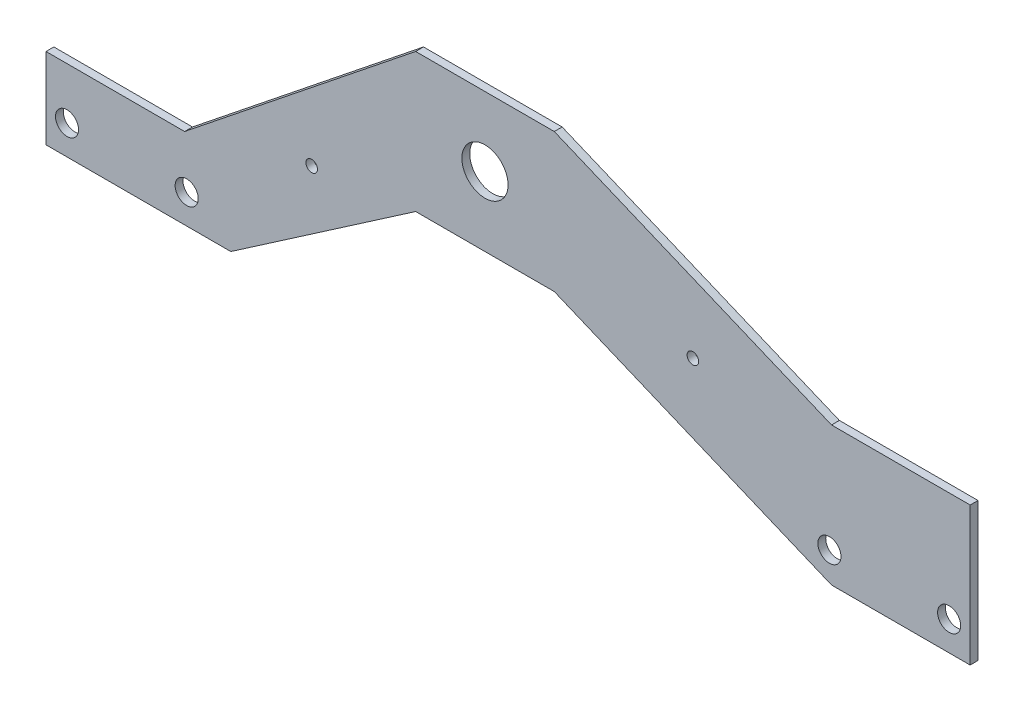
SolidWorks part; units mm, degrees
note: The reader was unsure of these and kept them because the rebuilt part matched: thickness of "Base-Flange1", "Sheet-Metal1", "Sheet-Metal2", "Sheet-Metal4".
material "1060 Alloy"
ref_plane "Front Plane" through (0, 0, 0) normal (0, 0, 1) x (1, 0, 0)
ref_plane "Top Plane" through (0, 0, 0) normal (0, 1, 0) x (1, 0, 0)
ref_plane "Right Plane" through (0, 0, 0) normal (1, 0, 0) x (0, 0, -1)
sketch "Sketch1" plane through (0, 0, 0) normal (0, 0, 1) x (1, 0, 0)
  line L0 (0, 0) -> (0, -35000)
  line L1 (0, -35000) -> (80000, -35000)
  line L2 (80000, -35000) -> (160000, 20000)
  line L3 (160000, 20000) -> (220000, 20000)
  line L4 (220000, 20000) -> (340000, -30000)
  line L5 (340000, -30000) -> (400000, -30000)
  line L6 (400000, -30000) -> (400000, 30000)
  line L7 (400000, 30000) -> (340000, 30000)
  line L8 (340000, 30000) -> (220000, 80000)
  line L9 (220000, 80000) -> (160000, 80000)
  line L10 (0, 0) -> (60000, 0)
  line L11 (160000, 80000) -> (60000, 0)
  line L12 (190000, 80000) -> (190000, 20000) construction
  line L13 (220000, 80000) -> (220000, 20000) construction
  line L14 (340000, 30000) -> (340000, -30000) construction
  line L15 (220000, 50000) -> (340000, 0) construction
  line L16 (100643.9259, 32515.1407) -> (129356.0741, -3375.0446) construction
  line L17 (115000, 14570.048) -> (190000, 50000) construction
  circle A0 centre (190000, 50000) radius 10000
  circle A1 centre (280000, 25000) radius 2500
  circle A2 centre (115000, 14570.048) radius 2500
  dimension "D12" = 20000
  dimension "D13" = 5000
  dimension "D14" = 5000
  dimension "D1" = 35000
  dimension "D2" = 80000
  dimension "D3" = 115000
  dimension "D4" = 60000
  dimension "D5" = 110000
  dimension "D6" = 60000
  dimension "D7" = 60000
  dimension "D8" = 60000
  dimension "D9" = 120000
  dimension "D10" = 80000
  dimension "D11" = 75000
base flange "Base-Flange1" sketch "Sketch1" thickness 3400 reverse thickness direction no parameters "D1"=0.7366
scale "Scale1" scale about centroid uniform scaling yes scale factor 0.001
sketch "Sketch2" plane through (0, 0, -1701.7) normal (0, 0, -1) x (-1, 0, 0)
  line L0 (-215477.869, 18112.8987) -> (-215477.869, 18077.8987)
  line L1 (-215477.869, 18077.8987) -> (-215557.869, 18077.8987)
  line L2 (-215512.869, 17958.5355) -> (-215512.869, 18112.8987) construction
  line L3 (-215512.869, 18090.5987) -> (-215538.769, 18090.5987) construction
  line L4 (-215537.869, 18112.8987) -> (-215477.869, 18112.8987) construction
  line L5 (-215477.869, 18112.8987) -> (-215557.869, 18112.8987)
  line L6 (-215877.869, 18082.8987) -> (-215842.869, 18082.8987)
  line L7 (-215842.869, 18082.8987) -> (-215842.869, 18095.5987) construction
  line L8 (-215842.869, 18095.5987) -> (-215868.769, 18095.5987) construction
  line L9 (-215557.869, 18112.8987) -> (-215557.869, 18077.8987)
  circle A0 centre (-215538.769, 18090.5987) radius 5
  circle A1 centre (-215486.969, 18090.5987) radius 5
  circle A2 centre (-215868.769, 18095.5987) radius 5
  circle A3 centre (-215816.969, 18095.5987) radius 5
  dimension "D1" = 25.9
  dimension "D2" = 25.9
  dimension "D3" = 12.7
  dimension "D4" = 35
  dimension "D5" = 12.7
  dimension "D6" = 35
extrude "Cut-Extrude1" cut sketch "Sketch2" against normal through all contours A1 | A0 | A3 | A2 normal cut yes
sketch "Bend-Lines1" [suppressed] plane through (0, 0, 0) normal (0, 1, 0) x (1, 0, 0)
sketch "Bounding-Box1" [suppressed] plane through (0, 0, 0) normal (0, 1, 0) x (1, 0, 0)
sheet metal parameters "Sheet-Metal1" thickness 3400 parameters "D1"=0.7366
flat pattern "Flat-Pattern1" [suppressed]
sketch "Bend-Lines2" plane through (0, 0, 0) normal (0, 1, 0) x (1, 0, 0)
sketch3d "Bounding-Box2" [suppressed]
  line L0 (76.2128, -37468.0385, 0) -> (421851.0288, -24443.6748, 0) construction
  line L1 (-5535.8602, 144270.6714, 0) -> (416238.9559, 157295.035, 0) construction
  line L2 (76.2128, -37468.0385, 0) -> (-5535.8602, 144270.6714, 0) construction
  line L3 (421851.0288, -24443.6748, 0) -> (416238.9559, 157295.035, 0) construction
sheet metal parameters "Sheet-Metal2" thickness 3400 parameters "D1"=0.7366
flat pattern "Flat-Pattern1"
sketch "Bend-Lines2" plane through (0, 0, 0) normal (0, 1, 0) x (1, 0, 0)
sketch3d "Bounding-Box2" [suppressed]
  line L0 (76.2128, -37468.0385, 0) -> (421851.0288, -24443.6748, 0) construction
  line L1 (-5535.8602, 144270.6714, 0) -> (416238.9559, 157295.035, 0) construction
  line L2 (76.2128, -37468.0385, 0) -> (-5535.8602, 144270.6714, 0) construction
  line L3 (421851.0288, -24443.6748, 0) -> (416238.9559, 157295.035, 0) construction
sheet metal parameters "Sheet-Metal4" thickness 3400 parameters "D1"=0.7366
flat pattern "Flat-Pattern1"
sketch "Bend-Lines2" plane through (0, 0, 0) normal (0, 1, 0) x (1, 0, 0)
sketch3d "Bounding-Box2" [suppressed]
  line L0 (76.2128, -37468.0385, 0) -> (421851.0288, -24443.6748, 0) construction
  line L1 (-5535.8602, 144270.6714, 0) -> (416238.9559, 157295.035, 0) construction
  line L2 (76.2128, -37468.0385, 0) -> (-5535.8602, 144270.6714, 0) construction
  line L3 (421851.0288, -24443.6748, 0) -> (416238.9559, 157295.035, 0) construction
